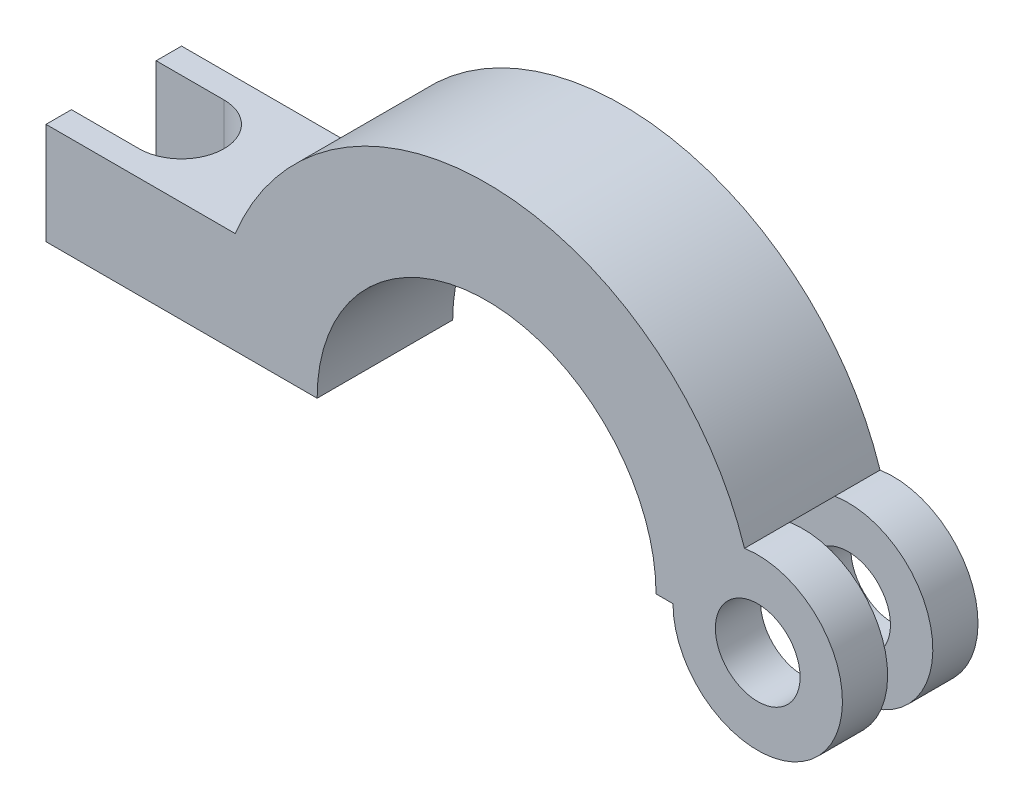
SolidWorks part; units mm, degrees
ref_plane "Front Plane" through (0, 0, 0) normal (0, 0, 1) x (1, 0, 0)
ref_plane "Top Plane" through (0, 0, 0) normal (0, 1, 0) x (1, 0, 0)
ref_plane "Right Plane" through (0, 0, 0) normal (1, 0, 0) x (0, 0, -1)
sketch "Sketch1" plane through (0, 0, 0) normal (0, 0, 1) x (1, 0, 0)
  line L0 (55, 0) -> (-55, 0) construction
  line L2 (-8, 0) -> (-13, 0)
  line L3 (-13, 0) -> (-13, 3)
  line L4 (-13, 3) -> (-7.4162, 3)
  line L5 (5, 0) -> (8, 0)
  line L6 (-8, 0) -> (-5, 0)
  arc A0 (-5, 0) -> (5, 0) centre (0, 0) cw
  arc A1 (-8, 0) -> (8, 0) centre (0, 0) cw
  dimension "D1" = 5
  dimension "D2" = 8
  dimension "D3" = 5
  dimension "D4" = 3
extrude "Boss-Extrude1" add sketch "Sketch1" along normal mid plane 4 contours A1 L6 A0 L5 | L2 A1 L4 L3 region at (-7.6771, 1.494, 0) region at (-10.4013, 1.5279, 0)
sketch "Sketch2" plane through (0, 0, 0) normal (0, 0, 1) x (1, 0, 0)
  line L0 (55, 0) -> (-55, 0) construction
  circle A0 centre (8, 0) radius 2.5
  arc A1 (8, 0) -> (-7.4162, 3) centre (0, 0) ccw construction
  dimension "D1" = 5
extrude "Boss-Extrude3" add sketch "Sketch2" along normal mid plane 4
sketch "Sketch3" plane through (0, 0, 2) normal (0, 0, 1) x (1, 0, 0)
  line L0 (55, 0) -> (-55, 0) construction
  circle A0 centre (8, 0) radius 1.25
  arc A1 (5.5, 0) -> (7.6094, 2.4693) centre (8, 0) ccw construction
  dimension "D1" = 2.5
  dimension "D2" = 0
extrude "Cut-Extrude1" cut sketch "Sketch3" against normal up to surface (4 mm away) up to face at (-2.3964, 2.2673, -2)
sketch "Sketch4" plane through (0, 0, 0) normal (0, 0, 1) x (1, 0, 0)
  circle A0 centre (8, 0) radius 2.5
  dimension "D1" = 5
extrude "Cut-Extrude2" cut sketch "Sketch4" against normal mid plane 1.3333
sketch "Sketch5" plane through (0, 3, 0) normal (0, 1, 0) x (1, 0, 0)
  line L0 (-13, 1.25) -> (-11, 1.25)
  line L1 (-13, -2) -> (-13, 2) construction
  line L2 (-13, -1.25) -> (-11, -1.25)
  line L3 (-44.2539, 0) -> (44.2539, 0) construction
  arc A0 (-11, 1.25) -> (-11, -1.25) centre (-11, 0) cw
  dimension "D1" = 1.25
  dimension "D2" = 0
  dimension "D3" = 2
extrude "Cut-Extrude3" cut sketch "Sketch5" along direction (0, 1, 0) on the side against the normal blind 3 and the other way through all
equation "\"InnerRad\"= 5"
equation "\"D1@Sketch1\"=\"InnerRad\""
equation "\"D2@Sketch1\"=\"InnerRad\"+3"
